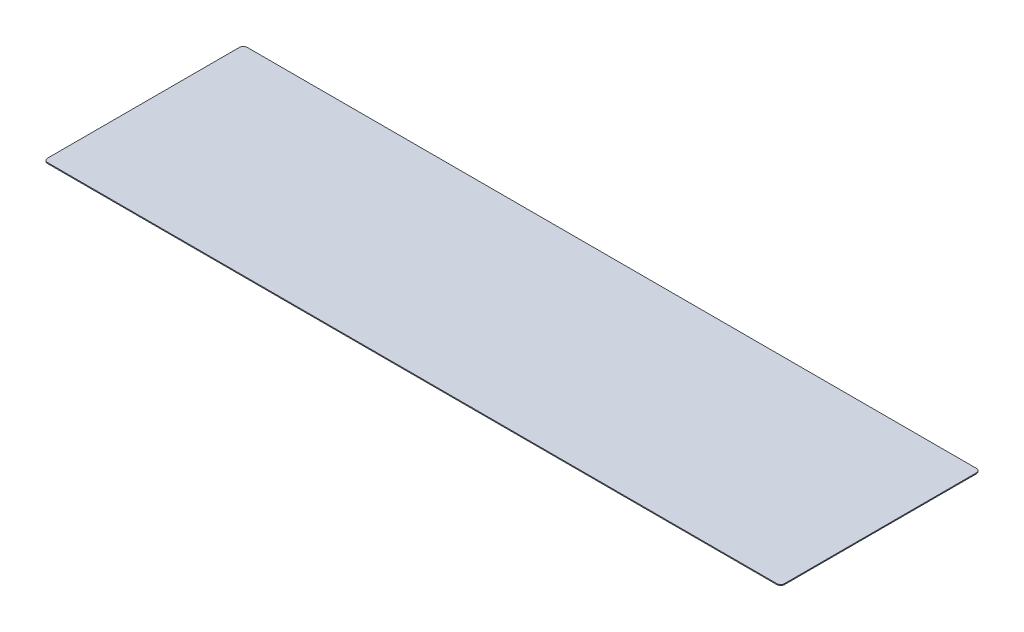
SolidWorks part; units mm, degrees
ref_plane "Front" through (0, 0, 0) normal (0, 0, 1) x (1, 0, 0)
ref_plane "Top" through (0, 0, 0) normal (0, 1, 0) x (1, 0, 0)
ref_plane "Right" through (0, 0, 0) normal (1, 0, 0) x (0, 0, -1)
sketch "Sketch1" plane through (0, 0, 0) normal (0, 1, 0) x (1, 0, 0)
  line L1 (6.35, 0) -> (1212.85, 0)
  line L2 (0, 6.35) -> (0, 323.85)
  line L3 (6.35, 330.2) -> (1212.85, 330.2)
  line L4 (1219.2, 6.35) -> (1219.2, 323.85)
  line L5 (0, 0) -> (1219.2, 330.2) construction
  line L6 (0, 330.2) -> (1219.2, 0) construction
  arc A0 (1212.85, 330.2) -> (1219.2, 323.85) centre (1212.85, 323.85) cw
  arc A1 (1212.85, 0) -> (1219.2, 6.35) centre (1212.85, 6.35) ccw
  arc A2 (6.35, 0) -> (0, 6.35) centre (6.35, 6.35) cw
  arc A3 (0, 323.85) -> (6.35, 330.2) centre (6.35, 323.85) cw
  point P4 (609.6, 165.1)
  dimension "D3" = 6.35
  dimension "D1" = 330.2
  dimension "D2" = 1219.2
extrude "Boss-Extrude1" add sketch "Sketch1" along normal blind 1.524
